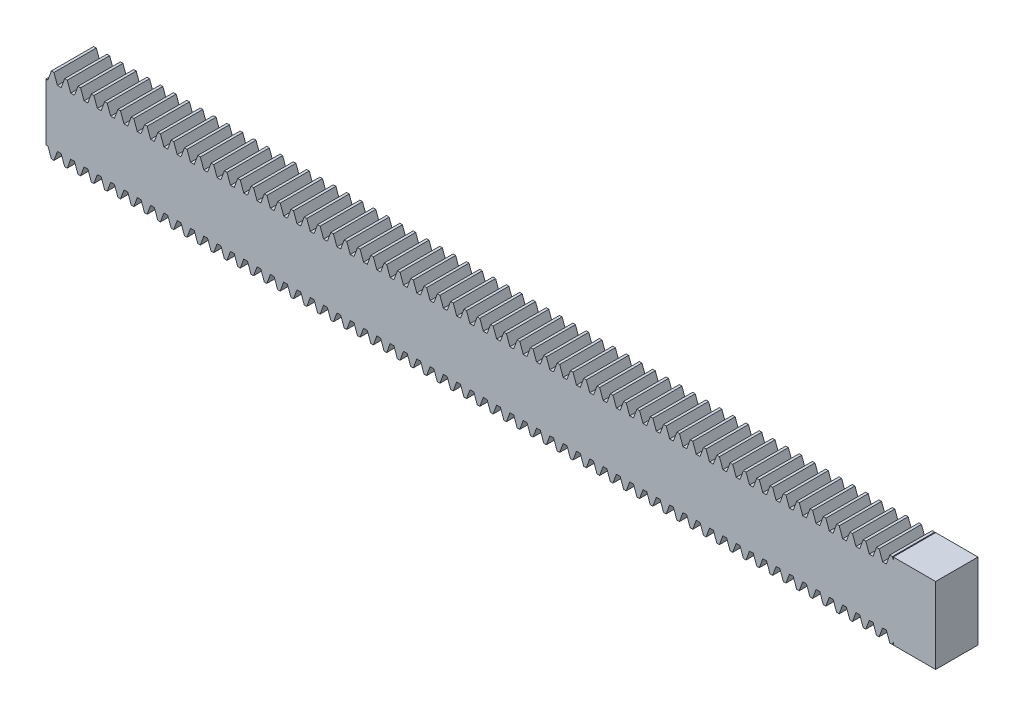
SolidWorks part; units mm, degrees
extrude "Blank" add sketch "BlankSke" against normal blind 10
sketch "BlankSke" plane through (0, 0, 0) normal (0, 0, 1) x (1, 0, 0)
  line L1 (0, 0) -> (200, 0)
  line L2 (0, 0) -> (0, 9)
  line L3 (0, 9) -> (200, 9)
  line L4 (200, 0) -> (200, 9)
  dimension "Length" = 200
ref_plane "Plane1" through (0, 0, 0) normal (0, 0, 1) x (1, 0, 0)
ref_plane "Plane2" through (0, 0, 0) normal (0, 1, 0) x (1, 0, 0)
ref_plane "Plane3" through (0, 0, 0) normal (1, 0, 0) x (0, 0, -1)
sketch "HoldingSke" plane through (0, 0, 0) normal (0, 1, 0) x (1, 0, 0)
  line L0 (0, 0) -> (0.1392, 0.9903)
  line L1 (-15, 0) -> (100, 0) construction
  line L2 (0, 0) -> (-2.1039, 2.3779)
  line L3 (0, 0) -> (-11.863, 4.5341)
  line L4 (0, 0) -> (3.6497, 7.8269)
  line L5 (0, 0) -> (-23.7986, -8.8762)
  line L6 (0, 0) -> (-10.5278, -7.1032)
  line L9 (-71.009, 38.7566) -> (116.9296, 107.1606)
  line L10 (-76.2, 3.3779) -> (-68.2, 3.3779)
  line L11 (0, 0) -> (-10, 0)
  line L12 (-76.2, 101.6) -> (-76.162, 101.6)
  line L13 (24.9733, 27.94) -> (52.9518, 28.4284)
  line L14 (24.9733, 27.94) -> (24.9743, 27.94)
  line L15 (24.9733, 27.94) -> (100.4006, 29.5858)
  circle A0 centre (0, 0) radius 19.05
  circle A1 centre (0, 0) radius 4
  circle A2 centre (0, 0) radius 12.7
  dimension "Num_teeth" = 65
  dimension "Width" = 10
  dimension "Length" = 200
  dimension "Pitch_height" = 8
sketch "TooCutSkeIll" plane through (0, 0, 0) normal (0, 0, 1) x (1, 0, 0)
  line L0 (-1.2538, 8.9737) -> (-0.5045, 6.9152)
  line L1 (-0.2687, 6.75) -> (0.2687, 6.75)
  line L2 (0.5045, 6.9152) -> (1.2538, 8.9737)
  line L3 (200, 9) -> (0, 9) construction
  line L4 (0, 0) -> (0, 64.897) construction
  line L5 (-13.208, 8) -> (12.954, 8) construction
  line L6 (0, 0) -> (200, 0) construction
  line L7 (0.8994, 8) -> (0.8994, 48.7463) construction
  line L8 (-0.8994, 8) -> (-0.8994, 48.7463) construction
  line L9 (1.2914, 9) -> (1.2914, 9.0254)
  line L10 (-1.2914, 9) -> (-1.2914, 9.0254)
  line L11 (-1.2914, 9.0254) -> (1.2914, 9.0254)
  arc A0 (0.2687, 6.75) -> (0.5045, 6.9152) centre (0.2687, 7.001) ccw
  arc A1 (-0.5045, 6.9152) -> (-0.2687, 6.75) centre (-0.2687, 7.001) ccw
  arc A2 (1.2914, 9) -> (1.2538, 8.9737) centre (1.2914, 8.96) ccw
  arc A3 (-1.2538, 8.9737) -> (-1.2914, 9) centre (-1.2914, 8.96) ccw
  dimension "Addendum_plus" = 1.0254
  dimension "Pitch_height" = 8
  dimension "Pressure_angle" = 20
  dimension "Gap_width" = 1.7988
  dimension "Dedendum" = 1.25
extrude "ToothCutIll" [suppressed] cut sketch "TooCutSkeIll" against normal through all
sketch "TooCutSkeSim" plane through (0, 0, 0) normal (0, 0, 1) x (1, 0, 0)
  line L0 (0.4444, 6.75) -> (-0.4444, 6.75)
  line L1 (1.2726, 9.0254) -> (0.4444, 6.75)
  line L2 (0, 17.4625) -> (0, 53.467) construction
  line L3 (1.2726, 9.0254) -> (-1.2726, 9.0254)
  line L6 (-1.2726, 9.0254) -> (-0.4444, 6.75)
  line L9 (-0.8994, 8) -> (0.8994, 8) construction
  line L10 (0, 0) -> (200, 0) construction
  line L11 (0.8994, 8) -> (0.8994, 53.467) construction
  line L12 (-0.8994, 8) -> (-0.8994, 53.467) construction
  dimension "Addendum_plus" = 1.0254
  dimension "Pitch_height" = 8
  dimension "Pressure_angle" = 20
  dimension "Gap_width" = 1.7988
  dimension "Dedendum" = 1.25
extrude "ToothCutSim" cut sketch "TooCutSkeSim" against normal through all
pattern_linear "TeethCuts" count 65 spacing 3.1416 along (1, 0, 0) of "ToothCutIll", "ToothCutSim"
mirror "Mirror1" about plane through (0, 0, 0) normal (0, 1, 0) of "TeethCuts", "ToothCutSim", "Blank"
sketch "Sketch1" plane through (200, 0, 0) normal (1, 0, 0) x (0, 0, -1)
  line L0 (10, -8.4466) -> (10, 8.4466) construction
  line L1 (0, -9) -> (10, -9)
  line L2 (0, -9) -> (0, 9)
  line L3 (0, 9) -> (10, 9)
  line L4 (10, -9) -> (10, 9)
  line L5 (0, -9) -> (10, 9) construction
  line L6 (0, 9) -> (10, -9) construction
  line L7 (10, 9) -> (0, 9) construction
  point P0 (5, 0)
  point P7 (10, 0)
  dimension "D1" = 18
  dimension "D2" = 10
  dimension "D3" = 0
  dimension "D4" = 0
extrude "Boss-Extrude1" add sketch "Sketch1" along normal blind 10
equation "' \"Module@HoldingSke\" = 6.35"
equation "' \"Num_teeth@HoldingSke\" = 12"
equation "' \"Ap@HoldingSke\" =  20"
equation "' \"Ap@HoldingSke\" = 20"
equation "' \"Width@HoldingSke\" = 0.25 * 25.4"
equation "' \"Show_teeth@HoldingSke\" = 500"
equation "' \"Backlash@HoldingSke\" = 0.009 * 25.4"
equation "' \"Addendum_fac@HoldingSke\" = 1.0"
equation "' \"Dedendum_fac@HoldingSke\" = 1.25"
equation "' \"Dedendum_add@HoldingSke\" = 0.00005 * 25.4"
equation "' \"Clearance_fac@HoldingSke\" = 0.25"
equation "' \"Pitch_height@HoldingSke\" = 1 * 25.4"
equation "' \"Length@HoldingSke\" = 4.71 * 25.4"
equation "\"Pitch@HoldingSke\" = 1 / \"Module@HoldingSke\""
equation "\"MPH@HoldingSke\" = \"Dedendum_fac@HoldingSke\" / \"Pitch@HoldingSke\" + 2 * \"Dedendum_add@HoldingSke\" + 0.002 * 25.4"
equation "\"MPH@HoldingSke\" = ((sgn( \"MPH@HoldingSke\" - \"Pitch_height@HoldingSke\")+1)*( \"MPH@HoldingSke\" - \"Pitch_height@HoldingSke\"))/2 + \"Pitch_height@HoldingSke\""
equation "\"Blank_height@BlankSke\" = \"Pitch_height@HoldingSke\" + \"Addendum_fac@HoldingSke\"  / \"Pitch@HoldingSke\" "
equation "\"Length@BlankSke\" =  \"Length@HoldingSke\""
equation "\"Face_width@Blank\" = \"Width@HoldingSke\""
equation "\"Pressure_angle@TooCutSkeIll\" = \"Ap@HoldingSke\""
equation "\"Addendum_plus@TooCutSkeIll\" =  \"Addendum_fac@HoldingSke\"  / \"Pitch@HoldingSke\" + 0.001 *25.4"
equation "\"Dedendum@TooCutSkeIll\" = \"Dedendum_fac@HoldingSke\"  / \"Pitch@HoldingSke\""
equation "\"Pitch_height@TooCutSkeIll\" =  \"MPH@HoldingSke\""
equation "\"Gap_width@TooCutSkeIll\" = 3.14159265 / 2 / \"Pitch@HoldingSke\" + 6 * \"Backlash@HoldingSke\""
equation "\"Pressure_angle@TooCutSkeSim\" = \"Ap@HoldingSke\""
equation "\"Addendum_plus@TooCutSkeSim\" =  \"Addendum_fac@HoldingSke\"  / \"Pitch@HoldingSke\" + 0.001 * 25.4"
equation "\"Dedendum@TooCutSkeSim\" = \"Dedendum_fac@HoldingSke\"  / \"Pitch@HoldingSke\""
equation "\"Pitch_height@TooCutSkeSim\" =  \"MPH@HoldingSke\""
equation "\"Gap_width@TooCutSkeSim\" = 3.14159265 / 2 / \"Pitch@HoldingSke\" + 6 * \"Backlash@HoldingSke\""
equation "\"Root_fillet@TooCutSkeIll\" = \"Clearance_fac@HoldingSke\" / \"Pitch@HoldingSke\" + \"Dedendum_add@HoldingSke\""
equation "\"Break_rad@TooCutSkeIll\" = 0.02 / \"Pitch@HoldingSke\" * 2"
equation "\"Linear_pitch@TeethCuts\" = 3.14159265 / \"Pitch@HoldingSke\""
equation "\"Num_teeth@HoldingSke\" = int( ( \"Length@HoldingSke\" + 0 ) / (3.14159265 / \"Pitch@HoldingSke\")) + 0.9999  + 1"
equation " \"Num_teeth@TeethCuts\" = int( \"Show_teeth@HoldingSke\" ) + 1"
equation " \"Num_teeth@TeethCuts\" = ((sgn( \"Num_teeth@TeethCuts\" - \"Num_teeth@HoldingSke\" )-1)*( \"Num_teeth@TeethCuts\" - \"Num_teeth@HoldingSke\" ))/-2+ \"Num_teeth@HoldingSke\""
equation " \"Num_teeth@TeethCuts\" = ((sgn( \"Num_teeth@TeethCuts\" - 2.0)+1)*( \"Num_teeth@TeethCuts\" - 2.0))/2 +2.0"
